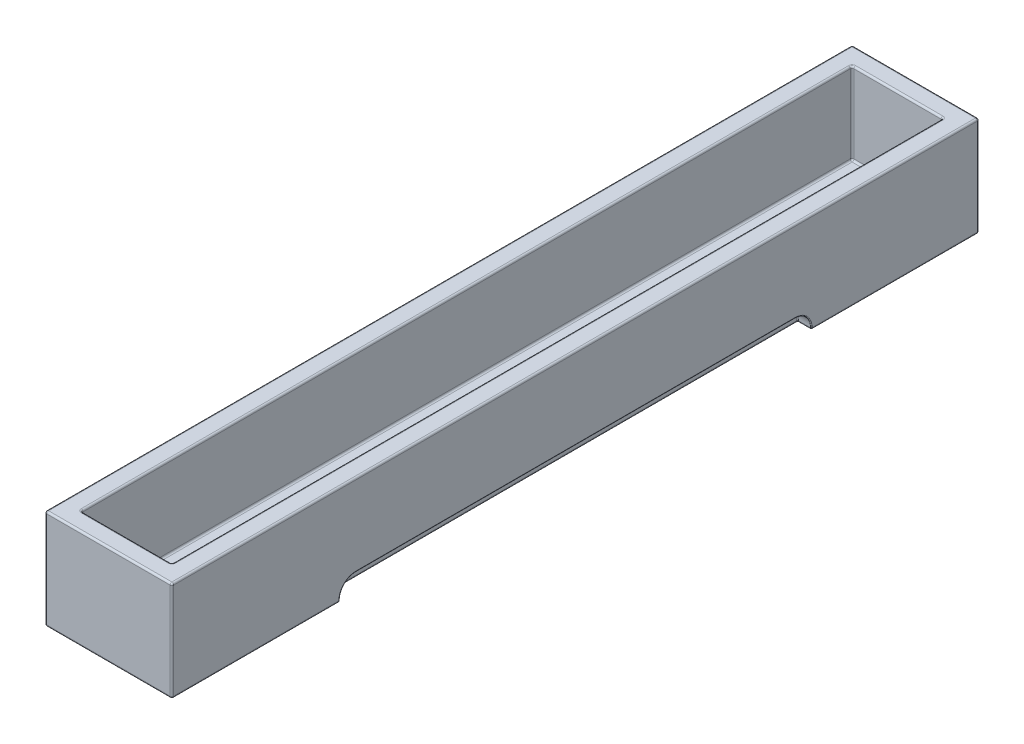
SolidWorks part; units mm, degrees
ref_plane "Front Plane" through (0, 0, 0) normal (0, 0, 1) x (1, 0, 0)
ref_plane "Top Plane" through (0, 0, 0) normal (0, 1, 0) x (1, 0, 0)
ref_plane "Right Plane" through (0, 0, 0) normal (1, 0, 0) x (0, 0, -1)
sketch "Sketch1" plane through (0, 0, 0) normal (1, 0, 0) x (0, 0, -1)
  line L1 (445, -55) -> (-445, -55)
  line L2 (445, -55) -> (445, 55)
  line L3 (445, 55) -> (-445, 55)
  line L4 (-445, -55) -> (-445, 55)
  line L5 (445, -55) -> (-445, 55) construction
  line L6 (445, 55) -> (-445, -55) construction
  point P0 (0, 0)
  dimension "D1" = 890
  dimension "D2" = 110
extrude "Boss-Extrude1" add sketch "Sketch1" against normal blind 140
sketch "Sketch2" plane through (0, 55, 0) normal (0, 1, 0) x (1, 0, 0)
  line L0 (-140, 445) -> (0, 445) construction
  line L1 (-120, 425) -> (-20, 425)
  line L2 (-120, 425) -> (-120, -425)
  line L3 (-120, -425) -> (-20, -425)
  line L4 (-20, 425) -> (-20, -425)
  line L5 (-140, 445) -> (-140, -445) construction
  line L6 (-140, -445) -> (0, -445) construction
  line L7 (0, 445) -> (0, -445) construction
  dimension "D1" = 20
  dimension "D2" = 20
  dimension "D3" = 20
  dimension "D4" = 20
extrude "Cut-Extrude1" cut sketch "Sketch2" against normal blind 90
sketch "Sketch3" plane through (0, 0, 0) normal (1, 0, 0) x (0, 0, -1)
  line L0 (-445, -55) -> (445, -55) construction
  line L1 (-260, -55) -> (260, -55)
  line L2 (-260, -55) -> (-260, -53)
  line L3 (-242, -35) -> (242, -35)
  line L4 (260, -55) -> (260, -53)
  arc A0 (242, -35) -> (260, -53) centre (242, -53) cw
  arc A1 (-260, -53) -> (-242, -35) centre (-242, -53) cw
  point P4 (0, -55)
  point P10 (260, -35)
  point P13 (-260, -35)
  dimension "D3" = 18
  dimension "D1" = 20
  dimension "D2" = 520
extrude "Cut-Extrude2" cut sketch "Sketch3" against normal blind 15
sketch "Sketch4" plane through (-15, 0, 0) normal (1, 0, 0) x (0, 0, -1)
  line L0 (-260, -55) -> (260, -55) construction
  line L1 (-130, -55) -> (130, -55)
  line L2 (-130, -55) -> (-130, -53)
  line L3 (-107, -30) -> (107, -30)
  line L4 (130, -55) -> (130, -53)
  arc A0 (107, -30) -> (130, -53) centre (107, -53) cw
  arc A1 (-130, -53) -> (-107, -30) centre (-107, -53) cw
  point P6 (0, -30)
  point P10 (130, -30)
  point P13 (-130, -30)
  dimension "D3" = 23
  dimension "D1" = 260
  dimension "D2" = 25
extrude "Cut-Extrude3" cut sketch "Sketch4" along normal blind 7
fillet "Fillet1" radius 1 20 edges at (-8, -31.2859, -114.5829) (-8, -30, 0) (0, -54, -260) (0, -40.2721, -254.7279) (0, -54, 260) (0, -40.2721, 254.7279) (-15, -31.2859, -114.5829) (-15, -31.2859, 114.5829) (-8, -31.2859, 114.5829) (0, -35, 0) (-8, -35, 0) (-15, -30, 0) (-15, -54, -260) (-15, -54, 260) (-15, -40.2721, -254.7279) (-15, -40.2721, 254.7279) (-15, -35, -181.6589) (-15, -35, 181.6589) (-11.5, -35, -121.3178) (-11.5, -35, 121.3178)
fillet "Fillet2" radius 2 32 edges at (-70, 55, -425) (-120, 10, -425) (-120, 55, 0) (-20, 10, -425) (-20, 55, 0) (-120, 10, 425) (-20, 10, 425) (-70, 55, 425) (-70, -35, -425) (-20, -35, 0) (-70, -35, 425) (-120, -35, 0) (-140, 55, 0) (-70, 55, -445) (-140, 0, -445) (-140, 0, 445) (-70, 55, 445) (-70, -55, -445) (-140, -55, 0) (-70, -55, 445) (-0.2929, -55, 260.2929) (-7.5, -55, 260) (-15, -55, 0) (-7.5, -55, -260) (-0.2929, -55, -260.2929) (0, -55, 353) (0, 0, 445) (0, 55, 0) (0, 0, -445) (0, -55, -353) (-14.7071, -55, 259.7071) (-14.7071, -55, -259.7071)
